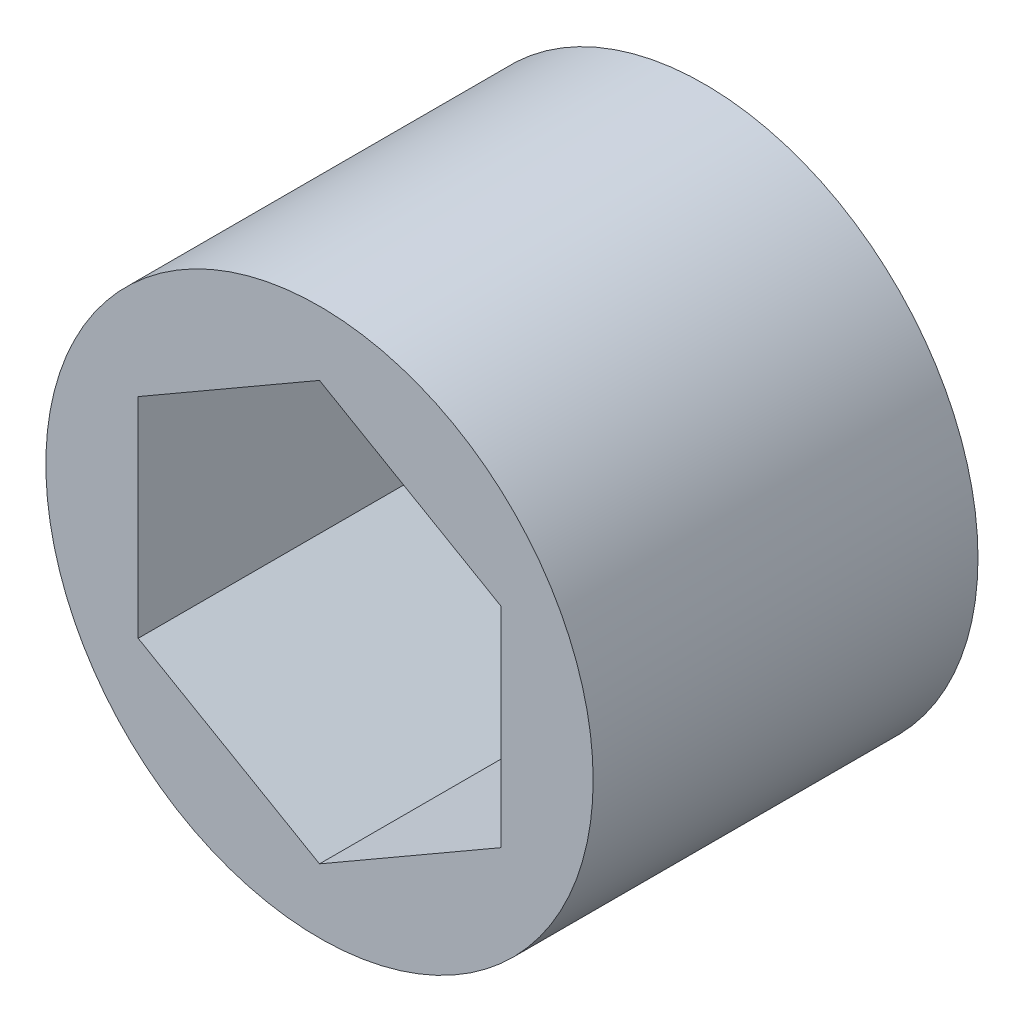
SolidWorks part; units mm, degrees
material "Nylon 101"
ref_plane "Front Plane" through (0, 0, 0) normal (0, 0, 1) x (1, 0, 0)
ref_plane "Top Plane" through (0, 0, 0) normal (0, 1, 0) x (1, 0, 0)
ref_plane "Right Plane" through (0, 0, 0) normal (1, 0, 0) x (0, 0, -1)
sketch "Sketch1" plane through (0, 0, 0) normal (0, 0, 1) x (1, 0, 0)
  line L1 (0, 7.7723) -> (-6.731, 3.8861)
  line L2 (-6.731, 3.8861) -> (-6.731, -3.8861)
  line L3 (-6.731, -3.8861) -> (0, -7.7723)
  line L4 (0, -7.7723) -> (6.731, -3.8861)
  line L5 (6.731, -3.8861) -> (6.731, 3.8861)
  line L6 (6.731, 3.8861) -> (0, 7.7723)
  circle A0 centre (0, 0) radius 10.16
  circle A1 centre (0, 0) radius 6.731 construction
  point P3 (0, 0)
  dimension "D1" = 20.32
  dimension "D2" = 13.462
extrude "Boss-Extrude1" add sketch "Sketch1" along normal mid plane 14.2875
